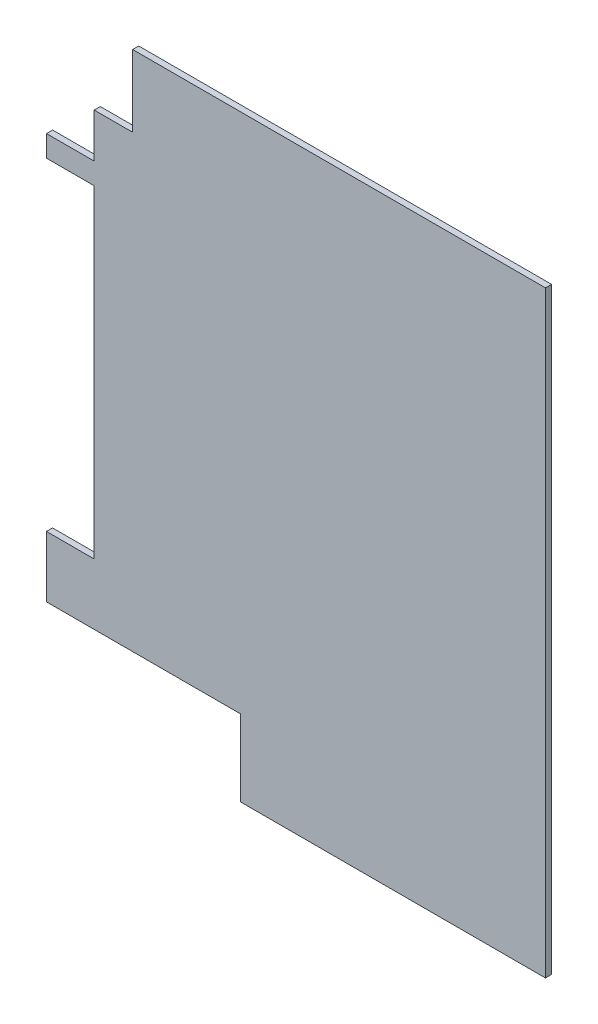
SolidWorks part; units mm, degrees
ref_plane "Front Plane" through (0, 0, 0) normal (0, 0, 1) x (1, 0, 0)
ref_plane "Top Plane" through (0, 0, 0) normal (0, 1, 0) x (1, 0, 0)
ref_plane "Right Plane" through (0, 0, 0) normal (1, 0, 0) x (0, 0, -1)
sketch "Sketch1" plane through (0, 0, 0) normal (0, 0, 1) x (1, 0, 0)
  line L0 (-5.7823, -13) -> (25.5, -13)
  line L2 (-5.7823, 1) -> (-5.7823, -13)
  line L5 (24.5, -14) -> (-24.5, -14) construction
  line L6 (321.5, -265) -> (321.5, 30)
  line L7 (-5.8246, -265) -> (65.6329, -265)
  line L8 (-5.8246, -265) -> (-5.8246, -225)
  line L11 (-5.8246, -265) -> (65.6329, -225) construction
  line L12 (-5.8246, -225) -> (65.6329, -265) construction
  line L15 (321.5, -265) -> (25.5, -265)
  line L16 (25.5, 1) -> (25.5, -265)
  line L17 (-5.8246, -225) -> (25.5, -225)
  line L18 (-24.5, -224) -> (24.5, -224) construction
  line L19 (-5.7823, 1) -> (25.5, 1)
  line L20 (24.5, -224) -> (24.5, -14) construction
  line L21 (-85.1981, 31) -> (50.7481, 31) construction
  line L23 (25.5, 1) -> (25.5, 30)
  line L24 (25.5, 30) -> (321.5, 30)
  line L27 (277.3251, 81) -> (277.3251, -319) construction
  line L28 (26.2777, -266) -> (-26.2882, -266) construction
  line L30 (-85.1981, 81) -> (277.3251, 81) construction
  line L31 (50.7481, 30) -> (321.5, 30)
  line L32 (50.7481, 30) -> (50.7481, 77)
  line L33 (50.7481, 77) -> (321.5, 77)
  line L34 (321.5, 30) -> (321.5, 77)
  line L35 (50.7481, 30) -> (321.5, 77) construction
  line L36 (50.7481, 77) -> (321.5, 30) construction
  line L37 (277.3251, -319) -> (-85.1981, -319) construction
  line L38 (321.5, -265) -> (121.5, -265)
  line L39 (321.5, -265) -> (321.5, -315)
  line L40 (321.5, -315) -> (121.5, -315)
  line L41 (121.5, -265) -> (121.5, -315)
  line L42 (321.5, -265) -> (121.5, -315) construction
  line L43 (321.5, -315) -> (121.5, -265) construction
  line L44 (50.7481, 31) -> (50.7481, -269) construction
  point P4 (32.4695, -6)
  point P10 (29.9042, -245)
  point P15 (48.1318, -132)
  point P24 (48.1318, 15.5)
  point P36 (186.1241, 53.5)
  point P42 (221.5, -290)
  dimension "D1" = 1
  dimension "D2" = 1
  dimension "D3" = 1
  dimension "D4" = 1
  dimension "D5" = 1
  dimension "D6" = 31.3246
  dimension "D7" = 296
  dimension "D8" = 4
  dimension "D9" = 200
  dimension "D10" = 4
extrude "Boss-Extrude1" add sketch "Sketch1" along normal blind 4 contours L24 L23 L16 L7 L15 L6 | L19 L2 L0 L16 | L17 L8 L7 L16 | L24 L34 L33 L32 | L15 L41 L40 L39 region at (9.8589, -6, 0) region at (173.5, -117.5, 0) region at (9.8377, -245, 0) region at (186.1241, 53.5, 0) region at (221.5, -290, 0)
